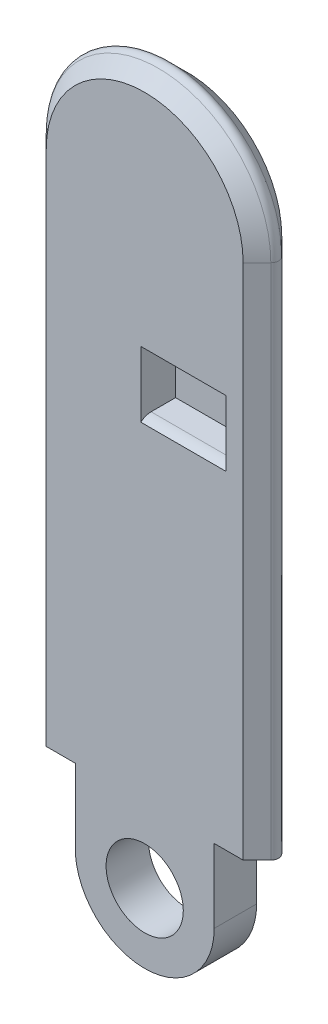
SolidWorks part; units mm, degrees
ref_plane "Płaszczyzna przednia" through (0, 0, 0) normal (0, 0, 1) x (1, 0, 0)
ref_plane "Płaszczyzna górna" through (0, 0, 0) normal (0, 1, 0) x (1, 0, 0)
ref_plane "Płaszczyzna prawa" through (0, 0, 0) normal (1, 0, 0) x (0, 0, -1)
sketch "Szkic1" plane through (0, 0, 0) normal (0, 0, 1) x (1, 0, 0)
  line L1 (-15.75, 33.5) -> (15.75, 33.5)
  line L2 (-15.75, 33.5) -> (-15.75, -33.5)
  line L3 (-15.75, -33.5) -> (15.75, -33.5)
  line L4 (15.75, 33.5) -> (15.75, -33.5)
  line L5 (-15.75, 33.5) -> (15.75, -33.5) construction
  line L6 (-15.75, -33.5) -> (15.75, 33.5) construction
  circle A0 centre (0, 33.5) radius 15.75
  point P0 (0, 0)
  dimension "D1" = 31.5
  dimension "D2" = 67
extrude "Dodanie-wyciągnięcie1" add sketch "Szkic1" against normal blind 6 contours L1 A0 | L1 A0 | A0 L2 L3 L4
chamfer "Sfazowanie1" distance 3.5 angle 45 6 edges at (15.75, 0, 0) (15.75, 0, -6) (0, 49.25, 0) (0, 49.25, -6) (-15.75, 0, 0) (-15.75, 0, -6)
fillet "Zaokrąglenie1" radius 1 3 edges at (15.25, 0, -3) (0, 48.75, -3) (-15.25, 0, -3)
sketch "Szkic2" plane through (0, 0, 0) normal (0, 0, 1) x (1, 0, 0)
  line L0 (-0.5, 12.25) -> (10.5, 12.25) construction
  line L1 (-10.6279, -13.75) -> (-5.9102, -13.75) construction
  line L10 (-0.5, 15) -> (-0.5, 9.5)
  line L11 (10.5, 9.5) -> (10.5, 15)
  line L12 (-0.5, 15) -> (10.5, 15)
  line L13 (-0.5, 9.5) -> (10.5, 9.5)
  line L14 (5, 15) -> (5, 9.5) construction
  point P15 (-8.269, -13.75)
  dimension "D1" = 5.5
  dimension "D2" = 11
  dimension "D3" = 5
  dimension "D4" = 13.75
  dimension "D5" = 26
extrude "Wytnij-wyciągnięcie1" cut sketch "Szkic2" against normal blind 5
sketch "Szkic3" plane through (0, 0, -6) normal (0, 0, -1) x (-1, 0, 0)
  line L0 (6, -8.6458) -> (6, -1.9889) construction
  line L1 (1.5, -5.2389) -> (10.5, -5.2389)
  line L2 (6, -24.2101) -> (6, -27.9889) construction
  line L3 (1.5, -5.2389) -> (1.5, 1.2611)
  line L4 (1.5, -31.2389) -> (10.5, -31.2389)
  line L5 (1.5, -31.2389) -> (1.5, -24.7389)
  line L6 (1.5, -24.7389) -> (10.5, -24.7389)
  line L7 (10.5, -31.2389) -> (10.5, -24.7389)
  line L8 (1.5, -31.2389) -> (10.5, -24.7389) construction
  line L9 (1.5, -24.7389) -> (10.5, -31.2389) construction
  line L10 (1.5, 1.2611) -> (10.5, 1.2611)
  line L11 (10.5, -5.2389) -> (10.5, 1.2611)
  line L12 (1.5, -5.2389) -> (10.5, 1.2611) construction
  line L13 (1.5, 1.2611) -> (10.5, -5.2389) construction
  line L14 (6, -27.9889) -> (6, -1.9889) construction
  dimension "D1" = 24.7389
  dimension "D2" = 9
  dimension "D3" = 6.5
  dimension "D4" = 9
  dimension "D5" = 6.5
  dimension "D6" = 6
  dimension "D7" = 26
extrude "Wytnij-wyciągnięcie2" cut sketch "Szkic3" against normal blind 4.5
chamfer "Sfazowanie2" distance 0.5 angle 45 1 edges at (-6, -24.7389, -6)
sketch "Szkic4" plane through (0, 0, 0) normal (0, 0, 1) x (1, 0, 0)
  line L0 (0, -33.5) -> (0, -43.0308) construction
  line L1 (-12.25, -33.5) -> (12.25, -33.5) construction
  line L2 (9, -43.0308) -> (9, -33.5)
  line L3 (9, -33.5) -> (-8.9747, -33.5)
  line L4 (-8.9747, -33.5) -> (-8.9747, -43.7054)
  circle A0 centre (0, -43.0308) radius 5
  circle A1 centre (0, -43.0308) radius 9
  dimension "D1" = 4
  dimension "D2" = 10
extrude "Dodanie-wyciągnięcie2" add sketch "Szkic4" against normal blind 6
sketch "Szkic5" plane through (0, 0, -6) normal (0, 0, -1) x (-1, 0, 0)
  line L3 (-5, 16) -> (0, 16)
  line L4 (0, 16) -> (0, -31)
  line L5 (-5, -31) -> (-5, 16)
  line L6 (-2.5, 16) -> (-2.5, -22.2858) construction
  line L8 (-0.5, 15) -> (-4.5, 15)
  line L9 (-0.5, 15) -> (-0.5, 9)
  line L10 (-0.5, 9) -> (-4.5, 9)
  line L11 (-4.5, 15) -> (-4.5, 9)
  line L12 (-0.5, 15) -> (-4.5, 9) construction
  line L13 (-0.5, 9) -> (-4.5, 15) construction
  point P6 (-2.5, 12)
  dimension "D1" = 1
  dimension "D2" = 0.5
  dimension "D3" = 6
  dimension "D4" = 5
  dimension "D5" = 16
  dimension "D6" = 2.5
extrude "Dodanie-wyciągnięcie3" add sketch "Szkic5" along normal blind 4.5 contours L8 L11 L10 L9
chamfer "Sfazowanie3" distance 3 angle 45 1 edges at (5, 15, 0)
chamfer "Sfazowanie4" distance 1 angle 45 1 edges at (5, 9.5, 0)
fillet "Zaokrąglenie2" radius 2 1 edges at (5, 9.5, -1)
sketch "Szkic6" plane through (0, 0, 0) normal (0, 0, 1) x (1, 0, 0)
  line L1 (-21.8406, 55.1915) -> (21.8406, 55.1915)
  line L2 (-21.8406, 55.1915) -> (-21.8406, -55.1915)
  line L3 (-21.8406, -55.1915) -> (21.8406, -55.1915)
  line L4 (21.8406, 55.1915) -> (21.8406, -55.1915)
  line L5 (-21.8406, 55.1915) -> (21.8406, -55.1915) construction
  line L6 (-21.8406, -55.1915) -> (21.8406, 55.1915) construction
  point P0 (0, 0)
extrude "Wytnij-wyciągnięcie3" cut sketch "Szkic6" against normal blind 0.5
